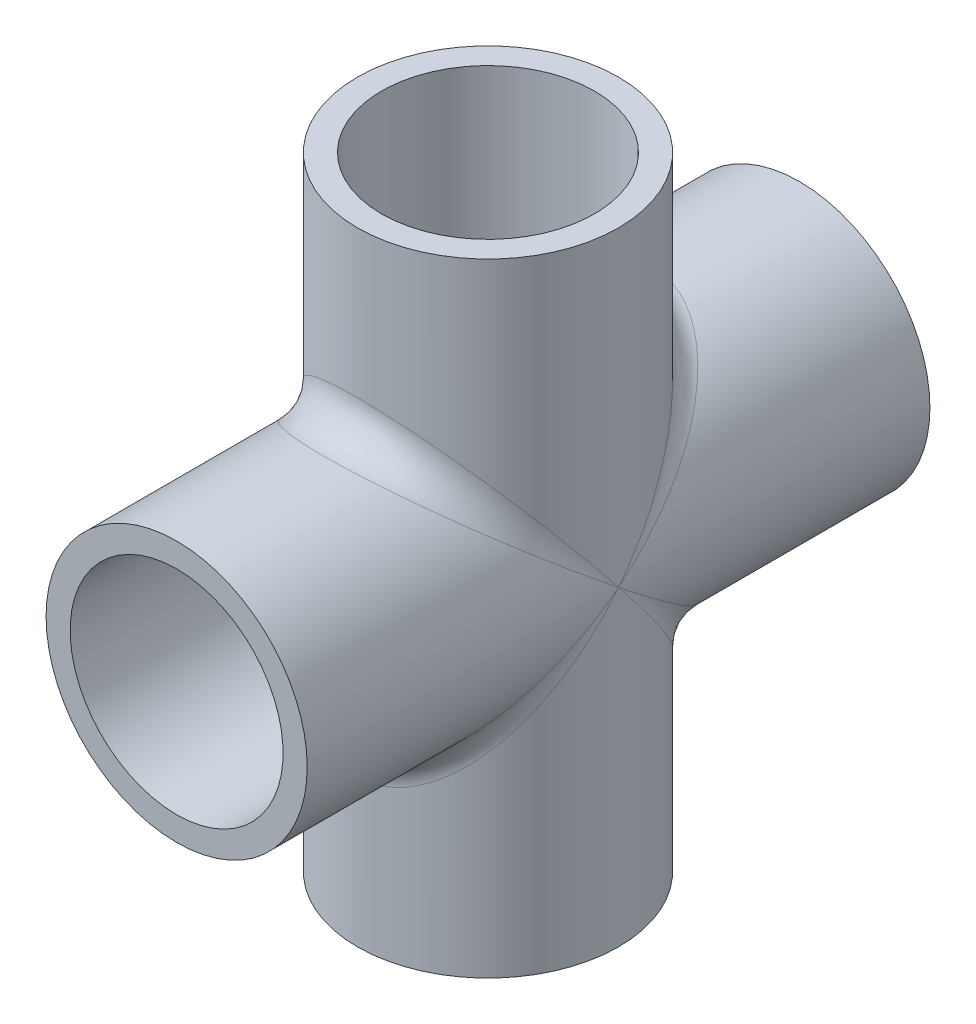
SolidWorks part; units mm, degrees
ref_plane "Front Plane" through (0, 0, 0) normal (0, 0, 1) x (1, 0, 0)
ref_plane "Top Plane" through (0, 0, 0) normal (0, 1, 0) x (1, 0, 0)
ref_plane "Right Plane" through (0, 0, 0) normal (1, 0, 0) x (0, 0, -1)
sketch "Sketch1" plane through (0, 0, 0) normal (1, 0, 0) x (0, 0, -1)
  line L0 (0, 0) -> (-49.2125, 0) construction
  line L1 (0, 0) -> (49.2125, 0) construction
  line L2 (0, 0) -> (0, 49.2125) construction
  line L3 (-20.6375, -13.3223) -> (-20.6375, 13.3223) construction
  line L4 (-13.3223, 20.6375) -> (13.3223, 20.6375) construction
  line L5 (20.6375, -13.3223) -> (20.6375, 13.3223) construction
  line L6 (-49.2125, -20.6375) -> (-49.2125, 20.6375) construction
  line L7 (49.2125, -20.6375) -> (49.2125, 20.6375) construction
  line L8 (20.6375, 49.2125) -> (-20.6375, 49.2125) construction
  line L9 (-20.6375, 13.3223) -> (-49.2125, 13.3223) construction
  line L10 (-13.3223, 20.6375) -> (-13.3223, 49.2125) construction
  line L11 (20.6375, 13.3223) -> (49.2125, 13.3223) construction
  line L12 (-34.925, -16.8275) -> (-34.925, 16.8275) construction
  line L13 (-16.8275, 34.925) -> (16.8275, 34.925) construction
  line L14 (34.925, -16.8275) -> (34.925, 16.8275) construction
  line L15 (0, 0) -> (0, -49.2125) construction
  line L16 (-20.6375, -49.2125) -> (20.6375, -49.2125) construction
  line L17 (-13.3223, -20.6375) -> (13.3223, -20.6375) construction
  line L18 (-16.8275, -34.925) -> (16.8275, -34.925) construction
  line L19 (13.3223, -20.6375) -> (13.3223, -49.2125) construction
  point P4 (0, 0)
  point P10 (-20.6375, 0)
  point P13 (0, 20.6375)
  point P16 (20.6375, 0)
  point P19 (-49.2125, 0)
  point P22 (49.2125, 0)
  point P25 (0, 49.2125)
  point P27 (-34.925, 13.3223)
  point P31 (-34.925, 0)
  point P34 (0, 34.925)
  point P37 (34.925, 0)
  point P38 (-13.3223, 34.925)
  point P39 (34.925, 13.3223)
  point P42 (0, -49.2125)
  point P46 (0, -20.6375)
  point P49 (0, -34.925)
  point P50 (13.3223, -34.925)
  dimension "Horz Leg Length" = 49.2125
  dimension "Vert Leg Length" = 49.2125
  dimension "Horz Length" = 98.425
  dimension "Horz Center to Socket" = 20.6375
  dimension "D1" = 20.6375
  dimension "Vert Center to Socket" = 20.6375
  dimension "Pipe ID" = 26.6446
  dimension "Tee OD" = 41.275
  dimension "For Pipe OD" = 33.655
  dimension "D2" = 20.6375
  dimension "Vert Length" = 98.425
sketch "Sketch2" plane through (0, 0, 0) normal (1, 0, 0) x (0, 0, -1)
  line L0 (-49.2125, 20.6375) -> (49.2125, 20.6375)
  line L1 (49.2125, 20.6375) -> (49.2125, 0)
  line L2 (49.2125, -20.6375) -> (49.2125, 20.6375) construction
  line L8 (-49.2125, -20.6375) -> (-49.2125, 20.6375) construction
  line L9 (-49.2125, 0) -> (-49.2125, 20.6375)
  line L10 (-49.2125, 0) -> (49.2125, 0)
revolve "Revolve1" add sketch "Sketch2" angle 360 about L0
sketch "Sketch3" plane through (0, 0, 0) normal (1, 0, 0) x (0, 0, -1)
  line L0 (0, 49.2125) -> (20.6375, 49.2125)
  line L1 (20.6375, 49.2125) -> (20.6375, -49.2125)
  line L3 (20.6375, -49.2125) -> (0, -49.2125)
  line L4 (0, -49.2125) -> (0, 49.2125)
revolve "Revolve2" add sketch "Sketch3" angle 360 about L2
sketch "Sketch4" plane through (0, 0, 0) normal (1, 0, 0) x (0, 0, -1)
  line L0 (-49.2125, 16.8275) -> (-20.6375, 16.8275)
  line L1 (-49.2125, -20.6375) -> (-49.2125, 20.6375) construction
  line L2 (-20.6375, 16.8275) -> (-20.6375, 13.3223)
  line L3 (-20.6375, 13.3223) -> (20.6375, 13.3223)
  line L4 (20.6375, 13.3223) -> (20.6375, 16.8275)
  line L5 (20.6375, 16.8275) -> (49.2125, 16.8275)
  line L6 (49.2125, -20.6375) -> (49.2125, 20.6375) construction
  line L7 (49.2125, 16.8275) -> (49.2125, 0)
  line L8 (49.2125, 0) -> (-49.2125, 0)
  line L9 (-49.2125, 0) -> (-49.2125, 16.8275)
revolve "Cut-Revolve1" cut sketch "Sketch4" angle 360 about L8
sketch "Sketch5" plane through (0, 0, 0) normal (1, 0, 0) x (0, 0, -1)
  line L0 (0, 49.2125) -> (0, -49.2125)
  line L1 (20.6375, 49.2125) -> (-20.6375, 49.2125) construction
  line L3 (0, -49.2125) -> (-16.8275, -49.2125)
  line L5 (-13.3223, -20.6375) -> (-13.3223, 20.6375)
  line L6 (-13.3223, 20.6375) -> (-16.8275, 20.6375)
  line L7 (-16.8275, 20.6375) -> (-16.8275, 49.2125)
  line L8 (-16.8275, 49.2125) -> (0, 49.2125)
  line L9 (-20.6375, -49.2125) -> (20.6375, -49.2125) construction
  line L10 (-16.8275, -49.2125) -> (-16.8275, -20.6375)
  line L11 (-16.8275, -20.6375) -> (-13.3223, -20.6375)
revolve "Cut-Revolve2" cut sketch "Sketch5" angle 360 about L0
fillet "Fillet1" radius 5.3258 4 edges at (0, -20.6375, -20.6375) (0, -20.6375, 20.6375) (0, 20.6375, 20.6375) (0, 20.6375, -20.6375)
sketch "Sketch6" plane through (0, 0, 0) normal (1, 0, 0) x (0, 0, -1)
  line L0 (-49.2125, 16.8275) -> (-20.6375, 16.8275)
  line L1 (-49.2125, -20.6375) -> (-49.2125, 20.6375) construction
  line L2 (-20.6375, 16.8275) -> (-20.6375, 13.3223)
  line L3 (-20.6375, 13.3223) -> (-13.3223, 13.3223)
  line L4 (-13.3223, 13.3223) -> (-13.3223, 20.6375)
  line L5 (-13.3223, 20.6375) -> (-16.8275, 20.6375)
  line L6 (-16.8275, 20.6375) -> (-16.8275, 49.2125)
  line L7 (20.6375, 49.2125) -> (-20.6375, 49.2125) construction
  line L8 (-20.6375, -13.3223) -> (-13.3223, -13.3223)
  line L9 (20.6375, -13.3223) -> (20.6375, -16.8275)
  line L10 (20.6375, -16.8275) -> (49.2125, -16.8275)
  line L11 (49.2125, -20.6375) -> (49.2125, 20.6375) construction
  line L12 (-20.6375, -13.3223) -> (-20.6375, -16.8275)
  line L13 (-20.6375, -16.8275) -> (-49.2125, -16.8275)
  line L14 (49.2125, 16.8275) -> (20.6375, 16.8275)
  line L15 (20.6375, 16.8275) -> (20.6375, 13.3223)
  line L16 (20.6375, 13.3223) -> (13.3223, 13.3223)
  line L17 (13.3223, 13.3223) -> (13.3223, 20.6375)
  line L18 (13.3223, 20.6375) -> (16.8275, 20.6375)
  line L19 (16.8275, 20.6375) -> (16.8275, 49.2125)
  line L20 (-13.3223, -20.6375) -> (-13.3223, -13.3223)
  line L21 (13.3223, -20.6375) -> (13.3223, -13.3223)
  line L22 (16.8275, -49.2125) -> (16.8275, -20.6375)
  line L23 (-20.6375, -49.2125) -> (20.6375, -49.2125) construction
  line L24 (16.8275, -20.6375) -> (13.3223, -20.6375)
  line L25 (-16.8275, -49.2125) -> (-16.8275, -20.6375)
  line L26 (-16.8275, -20.6375) -> (-13.3223, -20.6375)
  line L27 (13.3223, -13.3223) -> (20.6375, -13.3223)
sketch "Sketch7" plane through (0, 0, 49.2125) normal (0, 0, 1) x (1, 0, 0)
  circle A0 centre (0, 0) radius 16.8275 construction
  circle A1 centre (0, 0) radius 16.8275
  point P3 (0, -16.8275)
  point P4 (16.8275, 0)
  point P5 (-16.8275, 0)
  point P6 (0, 16.8275)
equation "\"D1@Fillet1\"=\"Tee OD@Sketch1\"*0.1290322581"
equation "\"D2@Sketch1\"=\"Vert Center to Socket@Sketch1\""
equation "\"Horz Leg Length@Sketch1\" = \"Horz Length@Sketch1\" / 2"
equation "\"Vert Leg Length@Sketch1\"=\"Vert Length@Sketch1\"/2"
equation "\"D1@Sketch1\"=\"Horz Center to Socket@Sketch1\""
